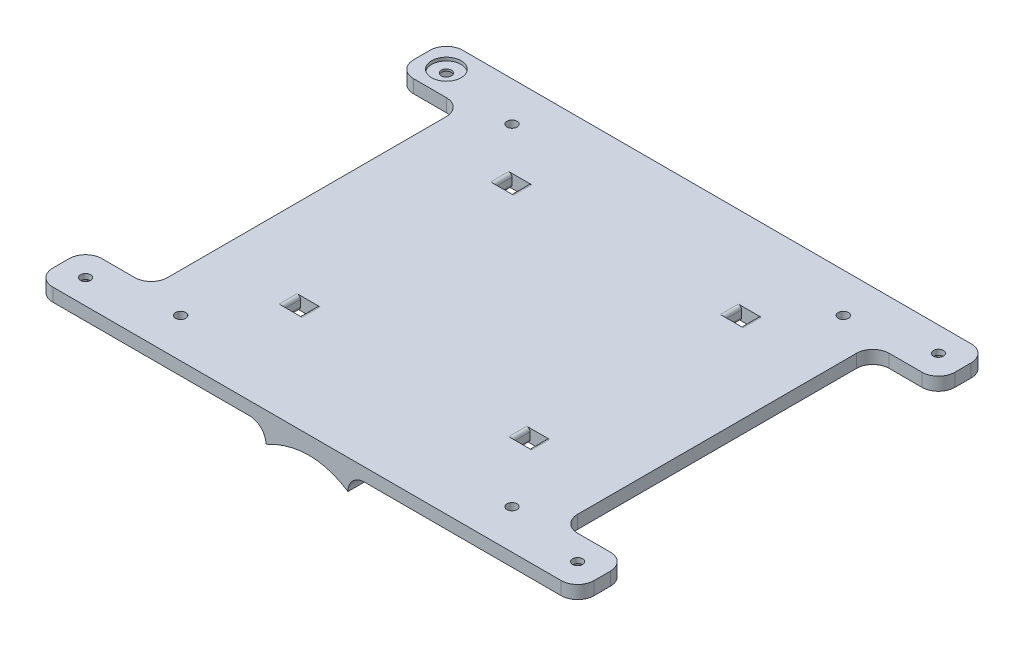
SolidWorks part; units mm, degrees
ref_plane "Front Plane" through (0, 0, 0) normal (0, 0, 1) x (1, 0, 0)
ref_plane "Top Plane" through (0, 0, 0) normal (0, 1, 0) x (1, 0, 0)
ref_plane "Right Plane" through (0, 0, 0) normal (1, 0, 0) x (0, 0, -1)
sketch "Sketch1" plane through (0, 0, 0) normal (0, 1, 0) x (1, 0, 0)
  line L0 (-79.307, 45.1379) -> (-79.307, -49.8621)
  line L1 (-68.307, -64.8621) -> (45.693, -64.8621)
  line L2 (45.693, -49.8621) -> (45.693, 45.1379)
  line L3 (45.693, 60.1379) -> (-68.307, 60.1379)
  line L4 (-68.307, 60.1379) -> (-99.307, 60.1379)
  line L5 (-99.307, 60.1379) -> (-99.307, 45.1379)
  line L6 (-99.307, 45.1379) -> (-79.307, 45.1379)
  line L7 (-68.307, -64.8621) -> (-99.307, -64.8621)
  line L8 (-99.307, -64.8621) -> (-99.307, -49.8621)
  line L9 (-99.307, -49.8621) -> (-79.307, -49.8621)
  line L10 (45.693, -64.8621) -> (65.693, -64.8621)
  line L11 (65.693, -64.8621) -> (65.693, -49.8621)
  line L12 (65.693, -49.8621) -> (45.693, -49.8621)
  line L13 (45.693, 60.1379) -> (65.693, 60.1379)
  line L14 (65.693, 60.1379) -> (65.693, 45.1379)
  line L15 (65.693, 45.1379) -> (45.693, 45.1379)
  dimension "D1" = 125
  dimension "D2" = 125
  dimension "D3" = 20
  dimension "D4" = 15
  dimension "D5" = 15
  dimension "D6" = 20
  dimension "D7" = 15
  dimension "D8" = 15
  dimension "D10" = 20
  dimension "D11" = 20
extrude "Boss-Extrude1" add sketch "Sketch1" along normal blind 4
sketch "Sketch2" plane through (0, 4, 0) normal (0, 1, 0) x (1, 0, 0)
  line L0 (-71.807, 52.6379) -> (-71.807, -57.3621)
  line L1 (-71.807, -57.3621) -> (38.193, -57.3621)
  line L2 (38.193, -57.3621) -> (38.193, 52.6379)
  line L3 (38.193, 52.6379) -> (-71.807, 52.6379)
  line L4 (-79.307, 45.1379) -> (-79.307, -49.8621) construction
  line L5 (-99.307, -64.8621) -> (65.693, -64.8621) construction
  line L6 (65.693, 60.1379) -> (-99.307, 60.1379) construction
  line L7 (45.693, -49.8621) -> (45.693, 45.1379) construction
  circle A0 centre (33.693, 48.1379) radius 1.55
  circle A1 centre (-67.307, 48.1379) radius 1.55
  circle A2 centre (-67.307, -52.8621) radius 1.55
  circle A3 centre (33.693, -52.8621) radius 1.55
  dimension "D8" = 110
  dimension "D1" = 7.5
  dimension "D2" = 7.5
  dimension "D3" = 110
  dimension "D4" = 101
  dimension "D5" = 4.5
  dimension "D6" = 101
  dimension "D7" = 4.5
  dimension "D9" = 7.5
  dimension "D10" = 7.5
  dimension "D11" = 4.5
  dimension "D12" = 4.5
extrude "Cut-Extrude3" cut sketch "Sketch2" against normal through all contours A1 | A0 | A3 | A2
sketch "Sketch4" plane through (-31.1286, 4, 0) normal (0, -1, 0) x (-1, 0, 0)
  line L0 (-19.1435, -1.7378) -> (-23.3424, -3.9435)
  line L1 (-3.6123, -3.9435) -> (-7.8102, -1.7378)
  line L2 (-7.8102, -6.1461) -> (-3.6123, -3.9435)
  line L3 (-23.3424, -3.9435) -> (-19.1435, -6.1461)
  line L4 (-19.1435, -7.1869) -> (-23.3424, -9.3906)
  line L5 (-3.6123, -9.3906) -> (-7.8102, -7.1869)
  line L6 (-7.8102, -11.5952) -> (-3.6123, -9.3906)
  line L7 (-23.3424, -9.3906) -> (-19.1435, -11.5952)
  line L8 (-19.1435, -12.635) -> (-23.3424, -14.8387)
  line L9 (-3.6123, -14.8387) -> (-7.8102, -12.635)
  line L10 (-7.8102, -17.0423) -> (-3.6123, -14.8387)
  line L11 (-23.3424, -14.8387) -> (-19.1435, -17.0423)
  line L12 (-7.5017, 11.7391) -> (-4.8823, 11.7391)
  line L13 (-10.0888, 5.39) -> (-10.0888, 7.6364)
  line L14 (-4.8823, 1.2873) -> (-7.5017, 1.2873)
  line L15 (-4.663, 11.5198) -> (-4.663, 1.5066)
  line L16 (-6.3249, 2.5097) -> (-6.3249, 10.5177)
  line L17 (-7.2487, 2.5097) -> (-6.3249, 2.5097)
  line L18 (-8.4041, 7.7514) -> (-8.4041, 5.2749)
  line L19 (-6.3249, 10.5177) -> (-7.2487, 10.5177)
  line L20 (-22.2342, 4.125) -> (-22.2342, 11.5198)
  line L21 (-16.8287, 11.5198) -> (-16.8287, 4.125)
  line L22 (-18.2714, 11.7391) -> (-17.048, 11.7391)
  line L23 (-18.4916, 4.127) -> (-18.4916, 11.5198)
  line L24 (-20.5713, 11.5198) -> (-20.5713, 4.127)
  line L25 (-22.0149, 11.7391) -> (-20.7905, 11.7391)
  line L26 (-14.3304, 10.4184) -> (-14.3304, 1.5066)
  line L27 (-15.903, 10.4184) -> (-14.3304, 10.4184)
  line L28 (-16.1228, 11.5198) -> (-16.1228, 10.6377)
  line L29 (-10.9808, 11.7391) -> (-15.903, 11.7391)
  line L30 (-10.7605, 10.6377) -> (-10.7605, 11.5198)
  line L31 (-12.5529, 10.4184) -> (-10.9808, 10.4184)
  line L32 (-12.5529, 1.5066) -> (-12.5529, 10.4184)
  line L33 (-14.1121, 1.2873) -> (-12.7722, 1.2873)
  spline S0 degree 3 poles (-7.8102, -1.7378) (-13.2484, -3.8532) (-13.7073, -3.8532) (-19.1435, -1.7378) knots 4 4 4 4 5 5 5 5
  spline S1 degree 3 poles (-19.1435, -6.1461) (-13.7073, -4.0318) (-13.2484, -4.0318) (-7.8102, -6.1461) knots 1 1 1 1 2 2 2 2
  spline S2 degree 3 poles (-7.8102, -7.1869) (-13.2484, -9.3013) (-13.7073, -9.3013) (-19.1435, -7.1869) knots 4 4 4 4 5 5 5 5
  spline S3 degree 3 poles (-19.1435, -11.5952) (-13.7073, -9.4799) (-13.2484, -9.4799) (-7.8102, -11.5952) knots 1 1 1 1 2 2 2 2
  spline S4 degree 3 poles (-7.8102, -12.635) (-13.2484, -14.7504) (-13.7073, -14.7504) (-19.1435, -12.635) knots 4 4 4 4 5 5 5 5
  spline S5 degree 3 poles (-19.1435, -17.0423) (-13.7073, -14.928) (-13.2484, -14.928) (-7.8102, -17.0423) knots 1 1 1 1 2 2 2 2
  spline S6 degree 3 poles (-9.5158, 11.0207) (-9.1398, 11.5079) (-8.5192, 11.7391) (-7.5017, 11.7391) knots 10 10 10 10 11 11 11 11
  spline S7 degree 3 poles (-10.0888, 7.6364) (-10.0888, 9.2824) (-10.0709, 10.3559) (-9.5158, 11.0207) knots 9 9 9 9 10 10 10 10
  spline S8 degree 3 poles (-9.5158, 2.0057) (-10.0709, 2.6705) (-10.0888, 3.744) (-10.0888, 5.39) knots 7 7 7 7 8 8 8 8
  spline S9 degree 3 poles (-7.5017, 1.2873) (-8.5192, 1.2873) (-9.1398, 1.5185) (-9.5158, 2.0057) knots 6 6 6 6 7 7 7 7
  spline S10 degree 3 poles (-4.7206, 1.3459) (-4.7558, 1.3112) (-4.8039, 1.2873) (-4.8823, 1.2873) knots 4 4 4 4 5 5 5 5
  spline S11 degree 3 poles (-4.663, 1.5066) (-4.663, 1.4282) (-4.6858, 1.3806) (-4.7206, 1.3459) knots 3 3 3 3 4 4 4 4
  spline S12 degree 3 poles (-4.7206, 11.6815) (-4.6858, 11.6458) (-4.663, 11.5992) (-4.663, 11.5198) knots 1 1 1 1 2 2 2 2
  spline S13 degree 3 poles (-4.8823, 11.7391) (-4.8039, 11.7391) (-4.7558, 11.7152) (-4.7206, 11.6815) knots 0 0 0 0 1 1 1 1
  spline S14 degree 3 poles (-8.0885, 2.8014) (-7.9, 2.5752) (-7.6565, 2.5097) (-7.2487, 2.5097) knots 5 5 5 5 6 6 6 6
  spline S15 degree 3 poles (-8.4041, 5.2749) (-8.4041, 3.8551) (-8.3793, 3.1507) (-8.0885, 2.8014) knots 4 4 4 4 5 5 5 5
  spline S16 degree 3 poles (-8.0885, 10.225) (-8.3793, 9.8757) (-8.4041, 9.1713) (-8.4041, 7.7514) knots 2 2 2 2 3 3 3 3
  spline S17 degree 3 poles (-7.2487, 10.5177) (-7.6565, 10.5177) (-7.9, 10.4512) (-8.0885, 10.225) knots 1 1 1 1 2 2 2 2
  spline S18 degree 3 poles (-21.6364, 1.9045) (-22.1156, 2.4611) (-22.2342, 3.1259) (-22.2342, 4.125) knots 20 20 20 20 21 21 21 21
  spline S19 degree 3 poles (-19.5364, 1.1554) (-20.5658, 1.1554) (-21.2286, 1.4312) (-21.6364, 1.9045) knots 19 19 19 19 20 20 20 20
  spline S20 degree 3 poles (-17.4027, 1.9035) (-17.8467, 1.4143) (-18.5189, 1.1554) (-19.5364, 1.1554) knots 18 18 18 18 19 19 19 19
  spline S21 degree 3 poles (-16.8287, 4.125) (-16.8287, 3.0485) (-16.9751, 2.3738) (-17.4027, 1.9035) knots 17 17 17 17 18 18 18 18
  spline S22 degree 3 poles (-16.8873, 11.6815) (-16.8515, 11.6458) (-16.8287, 11.5992) (-16.8287, 11.5198) knots 15 15 15 15 16 16 16 16
  spline S23 degree 3 poles (-17.048, 11.7391) (-16.9691, 11.7391) (-16.921, 11.7152) (-16.8873, 11.6815) knots 14 14 14 14 15 15 15 15
  spline S24 degree 3 poles (-18.4321, 11.6815) (-18.3984, 11.7152) (-18.3502, 11.7391) (-18.2714, 11.7391) knots 12 12 12 12 13 13 13 13
  spline S25 degree 3 poles (-18.4916, 11.5198) (-18.4916, 11.5992) (-18.4673, 11.6458) (-18.4321, 11.6815) knots 11 11 11 11 12 12 12 12
  spline S26 degree 3 poles (-18.8007, 2.6238) (-18.5636, 2.8848) (-18.4916, 3.3283) (-18.4916, 4.127) knots 9 9 9 9 10 10 10 10
  spline S27 degree 3 poles (-19.5151, 2.344) (-19.2085, 2.344) (-18.9773, 2.4294) (-18.8007, 2.6238) knots 8 8 8 8 9 9 9 9
  spline S28 degree 3 poles (-20.2627, 2.6218) (-20.0925, 2.4353) (-19.8514, 2.344) (-19.5151, 2.344) knots 7 7 7 7 8 8 8 8
  spline S29 degree 3 poles (-20.5713, 4.127) (-20.5713, 3.3561) (-20.5127, 2.8977) (-20.2627, 2.6218) knots 6 6 6 6 7 7 7 7
  spline S30 degree 3 poles (-20.6298, 11.6815) (-20.5946, 11.6458) (-20.5713, 11.5992) (-20.5713, 11.5198) knots 4 4 4 4 5 5 5 5
  spline S31 degree 3 poles (-20.7905, 11.7391) (-20.7122, 11.7391) (-20.6645, 11.7152) (-20.6298, 11.6815) knots 3 3 3 3 4 4 4 4
  spline S32 degree 3 poles (-22.1756, 11.6815) (-22.1414, 11.7152) (-22.0928, 11.7391) (-22.0149, 11.7391) knots 1 1 1 1 2 2 2 2
  spline S33 degree 3 poles (-22.2342, 11.5198) (-22.2342, 11.5992) (-22.2104, 11.6458) (-22.1756, 11.6815) knots 0 0 0 0 1 1 1 1
  spline S34 degree 3 poles (-16.0652, 10.476) (-16.03, 10.4413) (-15.9819, 10.4184) (-15.903, 10.4184) knots 17 17 17 17 18 18 18 18
  spline S35 degree 3 poles (-16.1228, 10.6377) (-16.1228, 10.5593) (-16.0985, 10.5107) (-16.0652, 10.476) knots 16 16 16 16 17 17 17 17
  spline S36 degree 3 poles (-16.0652, 11.6815) (-16.0985, 11.6458) (-16.1228, 11.5992) (-16.1228, 11.5198) knots 14 14 14 14 15 15 15 15
  spline S37 degree 3 poles (-15.903, 11.7391) (-15.9819, 11.7391) (-16.03, 11.7152) (-16.0652, 11.6815) knots 13 13 13 13 14 14 14 14
  spline S38 degree 3 poles (-10.819, 11.6815) (-10.8548, 11.7152) (-10.9019, 11.7391) (-10.9808, 11.7391) knots 11 11 11 11 12 12 12 12
  spline S39 degree 3 poles (-10.7605, 11.5198) (-10.7605, 11.5992) (-10.7843, 11.6458) (-10.819, 11.6815) knots 10 10 10 10 11 11 11 11
  spline S40 degree 3 poles (-10.819, 10.476) (-10.7843, 10.5107) (-10.7605, 10.5593) (-10.7605, 10.6377) knots 8 8 8 8 9 9 9 9
  spline S41 degree 3 poles (-10.9808, 10.4184) (-10.9019, 10.4184) (-10.8548, 10.4413) (-10.819, 10.476) knots 7 7 7 7 8 8 8 8
  spline S42 degree 3 poles (-12.6114, 1.3459) (-12.5757, 1.3806) (-12.5529, 1.4282) (-12.5529, 1.5066) knots 4 4 4 4 5 5 5 5
  spline S43 degree 3 poles (-12.7722, 1.2873) (-12.6943, 1.2873) (-12.6457, 1.3112) (-12.6114, 1.3459) knots 3 3 3 3 4 4 4 4
  spline S44 degree 3 poles (-14.2729, 1.3459) (-14.2376, 1.3112) (-14.19, 1.2873) (-14.1121, 1.2873) knots 1 1 1 1 2 2 2 2
  spline S45 degree 3 poles (-14.3304, 1.5066) (-14.3304, 1.4282) (-14.3076, 1.3806) (-14.2729, 1.3459) knots 0 0 0 0 1 1 1 1
extrude "Boss-Extrude2" [suppressed] add sketch "Sketch4" against normal blind 1.6
fillet "Fillet1" radius 5 12 edges at (-99.307, 2, -45.1379) (-99.307, 2, -60.1379) (-99.307, 2, 64.8621) (65.693, 2, -60.1379) (45.693, 2, -45.1379) (65.693, 2, -45.1379) (65.693, 2, 64.8621) (-99.307, 2, 49.8621) (65.693, 2, 49.8621) (45.693, 2, 49.8621) (-79.307, 2, 49.8621) (-79.307, 2, -45.1379)
sketch "Sketch5" plane through (0, 4, 0) normal (0, 1, 0) x (1, 0, 0)
  line L0 (60.693, 60.1379) -> (-94.307, 60.1379) construction
  line L1 (-99.307, 55.1379) -> (-99.307, 50.1379) construction
  line L2 (-84.307, -49.8621) -> (-94.307, -49.8621) construction
  line L3 (-99.307, -54.8621) -> (-99.307, -59.8621) construction
  line L4 (60.693, -49.8621) -> (50.693, -49.8621) construction
  line L5 (65.693, -59.8621) -> (65.693, -54.8621) construction
  line L6 (65.693, 50.1379) -> (65.693, 55.1379) construction
  circle A0 centre (-91.807, 52.6379) radius 1.525
  circle A1 centre (-91.807, 52.6379) radius 4.5
  circle A2 centre (-91.807, -57.3621) radius 1.525
  circle A3 centre (58.193, -57.3621) radius 1.525
  circle A4 centre (58.193, 52.6379) radius 1.525
  dimension "D1" = 3.05
  dimension "D4" = 9
  dimension "D7" = 3.05
  dimension "D10" = 3.05
  dimension "D13" = 3.05
  dimension "D2" = 7.5
  dimension "D3" = 7.5
  dimension "D5" = 7.5
  dimension "D6" = 7.5
  dimension "D8" = 7.5
  dimension "D9" = 7.5
  dimension "D11" = 7.5
  dimension "D12" = 7.5
extrude "Cut-Extrude4" cut sketch "Sketch5" against normal blind 10 contours A0 | A2 | A3 | A4
extrude "Cut-Extrude5" cut sketch "Sketch5<3>" against normal blind 1 contours A1
sketch "Sketch5<3>" plane through (0, 4, 0) normal (0, 1, 0) x (1, 0, 0) same geometry as "Sketch5"
sketch "Sketch6" plane through (0, 0, 0) normal (0, -1, 0) x (1, 0, 0)
  line L1 (-88.6369, 56.8955) -> (-89.8179, 59.8742)
  line L2 (-89.8179, 59.8742) -> (-92.988, 60.3408)
  line L3 (-92.988, 60.3408) -> (-94.9772, 57.8287)
  line L4 (-94.9772, 57.8287) -> (-93.7962, 54.8499)
  line L5 (-93.7962, 54.8499) -> (-90.626, 54.3834)
  line L6 (-90.626, 54.3834) -> (-88.6369, 56.8955)
  line L7 (61.3753, 56.9877) -> (60.1084, 59.9309)
  line L8 (60.1084, 59.9309) -> (56.926, 60.3052)
  line L9 (56.926, 60.3052) -> (55.0106, 57.7364)
  line L10 (55.0106, 57.7364) -> (56.2776, 54.7933)
  line L11 (56.2776, 54.7933) -> (59.46, 54.4189)
  line L12 (59.46, 54.4189) -> (61.3753, 56.9877)
  line L13 (60.6824, -50.6205) -> (57.6905, -49.4733)
  line L14 (57.6905, -49.4733) -> (55.2011, -51.4908)
  line L15 (55.2011, -51.4908) -> (55.7035, -54.6554)
  line L16 (55.7035, -54.6554) -> (58.6955, -55.8026)
  line L17 (58.6955, -55.8026) -> (61.1849, -53.7851)
  line L18 (61.1849, -53.7851) -> (60.6824, -50.6205)
  line L19 (-88.7407, -51.7078) -> (-91.0794, -49.5174)
  line L20 (-91.0794, -49.5174) -> (-94.1457, -50.4475)
  line L21 (-94.1457, -50.4475) -> (-94.8733, -53.568)
  line L22 (-94.8733, -53.568) -> (-92.5347, -55.7585)
  line L23 (-92.5347, -55.7585) -> (-89.4683, -54.8284)
  line L24 (-89.4683, -54.8284) -> (-88.7407, -51.7078)
  circle A0 centre (-91.807, 57.3621) radius 2.775 construction
  circle A1 centre (58.193, 57.3621) radius 2.775 construction
  circle A2 centre (58.193, -52.6379) radius 2.775 construction
  circle A3 centre (-91.807, -52.6379) radius 2.775 construction
  circle A4 centre (58.193, -52.6379) radius 1.525 construction
  point P40 (-89.1045, -53.2681)
  dimension "D1" = 5.55
  dimension "D2" = 5.55
  dimension "D3" = 5.55
  dimension "D4" = 5.55
extrude "Cut-Extrude6" cut sketch "Sketch6" against normal blind 2.4
sketch "Sketch8" plane through (0, 0, 0) normal (0, -1, 0) x (1, 0, 0)
  line L0 (-4.307, -60.1379) -> (-4.307, 64.8621)
  line L1 (60.693, -60.1379) -> (-94.307, -60.1379) construction
  line L2 (-94.307, 64.8621) -> (60.693, 64.8621) construction
  line L3 (-4.307, 64.8621) -> (-29.307, 64.8621)
  line L4 (-29.307, 64.8621) -> (-29.307, -60.1379)
  line L5 (-29.307, -60.1379) -> (-4.307, -60.1379)
  line L6 (-16.807, 64.8621) -> (-16.807, -66.1895) construction
  line L7 (-94.307, 64.8621) -> (60.693, 64.8621) construction
  dimension "D1" = 25
  dimension "D2" = 12.5
extrude "Boss-Extrude4" add sketch "Sketch8" along normal blind 5
sketch "Sketch9" plane through (0, 0, 64.8621) normal (0, 0, 1) x (1, 0, 0)
  line L0 (-4.307, -5) -> (-29.307, -5)
  spline S0 degree 2 poles (-4.307, -5) (-15.5927, 2.2701) (-29.307, -5) knots 0 0 0 1 1 1
  dimension "D1" = 2.5
extrude "Cut-Extrude7" cut sketch "Sketch9" against normal through all
fillet "Fillet5" radius 5 2 edges at (-29.307, 0, 2.3621) (-4.307, 0, 2.3621)
sketch "Sketch10" plane through (0, 0, 0) normal (0, -1, 0) x (1, 0, 0)
  line L0 (20.693, -35.1379) -> (20.693, -29.6379)
  line L1 (20.693, -29.6379) -> (15.693, -29.6379)
  line L2 (15.693, -29.6379) -> (15.693, -35.1379)
  line L3 (15.693, -35.1379) -> (20.693, -35.1379)
  line L4 (-16.807, 64.8621) -> (-16.807, -60.1379) construction
  line L5 (-4.307, 64.8621) -> (-29.307, 64.8621) construction
  line L6 (-29.307, -60.1379) -> (-4.307, -60.1379) construction
  line L7 (20.693, 29.3621) -> (20.693, 34.8621)
  line L8 (20.693, 34.8621) -> (15.693, 34.8621)
  line L9 (15.693, 34.8621) -> (15.693, 29.3621)
  line L10 (15.693, 29.3621) -> (20.693, 29.3621)
  line L11 (45.693, 44.8621) -> (45.693, -40.1379) construction
  line L12 (60.693, -60.1379) -> (0.693, -60.1379) construction
  line L13 (0.693, 64.8621) -> (60.693, 64.8621) construction
  line L15 (-49.307, 29.3621) -> (-54.307, 29.3621)
  line L16 (-49.307, 34.8621) -> (-49.307, 29.3621)
  line L17 (-54.307, 34.8621) -> (-49.307, 34.8621)
  line L18 (-54.307, 29.3621) -> (-54.307, 34.8621)
  line L19 (-49.307, -35.1379) -> (-54.307, -35.1379)
  line L20 (-49.307, -29.6379) -> (-49.307, -35.1379)
  line L21 (-54.307, -29.6379) -> (-49.307, -29.6379)
  line L22 (-54.307, -35.1379) -> (-54.307, -29.6379)
  dimension "D1" = 5
  dimension "D2" = 5.5
  dimension "D3" = 5.5
  dimension "D4" = 25
  dimension "D5" = 25
  dimension "D6" = 5
  dimension "D7" = 25
  dimension "D8" = 30
extrude "Cut-Extrude8" cut sketch "Sketch10" against normal blind 5
fillet "Fillet7" radius 1 16 edges at (15.693, 4, -32.3879) (15.693, 0, -32.3879) (-49.307, 0, -32.3879) (-49.307, 4, -32.3879) (-54.307, 0, -32.3879) (-54.307, 4, -32.3879) (15.693, 0, 32.1121) (15.693, 4, 32.1121) (-49.307, 0, 32.1121) (-49.307, 4, 32.1121) (-54.307, 0, 32.1121) (-54.307, 4, 32.1121) (20.693, 0, 32.1121) (20.693, 4, 32.1121) (20.693, 0, -32.3879) (20.693, 4, -32.3879)
equation "\"1.6.00mm\"=2"
